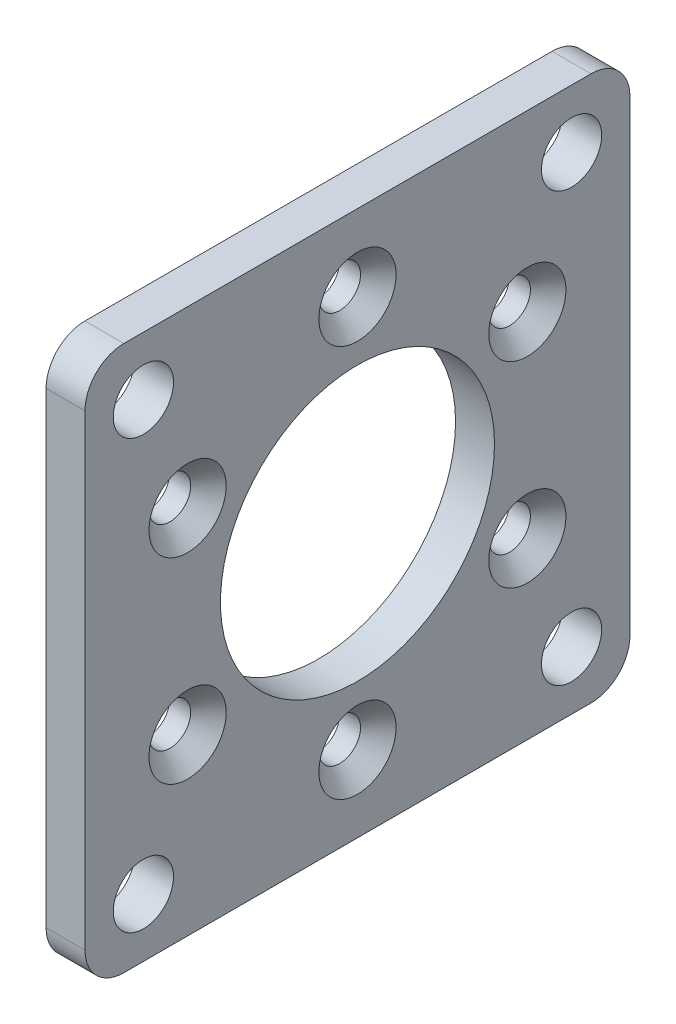
SolidWorks part; units mm, degrees
ref_plane "Front" through (0, 0, 0) normal (0, 0, 1) x (1, 0, 0)
ref_plane "Top" through (0, 0, 0) normal (0, 1, 0) x (1, 0, 0)
ref_plane "Right" through (0, 0, 0) normal (1, 0, 0) x (0, 0, -1)
sketch "Sketch1" plane through (0, 0, 0) normal (1, 0, 0) x (0, 0, -1)
  line L1 (22.225, -22.225) -> (-22.225, -22.225)
  line L2 (22.225, -22.225) -> (22.225, 22.225)
  line L3 (22.225, 22.225) -> (-22.225, 22.225)
  line L4 (-22.225, -22.225) -> (-22.225, 22.225)
  line L5 (22.225, -22.225) -> (-22.225, 22.225) construction
  line L6 (22.225, 22.225) -> (-22.225, -22.225) construction
  circle A0 centre (0, 0) radius 11.176
  dimension "D1" = 22.352
  dimension "D2" = 44.45
  dimension "D3" = 44.45
extrude "Boss-Extrude1" add sketch "Sketch1" along normal blind 3.175
sketch "Sketch4" plane through (3.175, 0, 0) normal (1, 0, 0) x (0, 0, -1)
  line L1 (22.225, 22.225) -> (-22.225, 22.225) construction
  line L2 (-22.225, 22.225) -> (-22.225, -22.225) construction
  line L3 (22.225, -22.225) -> (22.225, 22.225) construction
  line L4 (-22.225, -22.225) -> (22.225, -22.225) construction
  point P0 (-17.4625, 17.4625)
  point P2 (17.4625, 17.4625)
  point P4 (17.4625, -17.4625)
  point P6 (-17.4625, -17.4625)
  point P17 (-16.1195, 17.7425)
  point P18 (14.7376, 17.7425)
  point P19 (-17.7768, -17.2471)
  dimension "D1" = 4.7625
  dimension "D2" = 4.7625
  dimension "D3" = 4.7625
  dimension "D4" = 4.7625
hole_wizard "#10 (0.1935) Diameter Hole1" positions "Sketch4" profile "Sketch3" hole size "#10" standard "ANSI Inch" end condition up to next
sketch "Sketch3" plane through (3.175, 17.4625, 17.4625) normal (0, 1, 0) x (0, 0, -1)
  line L0 (0, 0) -> (0, 3.175)
  line L1 (0, 3.175) -> (2.4574, 3.175)
  line L2 (2.4574, 3.175) -> (2.4574, 0)
  line L5 (2.4574, 0) -> (0, 0)
  line L11 (0, -6.35) -> (0, 107.95) construction
  dimension "Thru Hole Dia." = 4.9149
  dimension "Thru Hole Depth" = 3.175
sketch "Sketch7" plane through (3.175, 0, 0) normal (1, 0, 0) x (0, 0, -1)
  circle A0 centre (0, 0) radius 16 construction
  point P5 (0, 16)
  point P11 (13.8564, 8)
  point P12 (13.8564, -8)
  point P13 (0, -16)
  point P14 (-13.8564, -8)
  point P15 (-13.8564, 8)
  dimension "D2" = 32
  dimension "D1" = 6
hole_wizard "CSK for M3 Flat Head Machine Screw1" positions "Sketch7" profile "Sketch6" countersink size "M3" standard "ANSI Metric" end condition up to next
sketch "Sketch6" plane through (3.175, 8, 13.8564) normal (0, 1, 0) x (0, 0, -1)
  line L0 (0, 0) -> (0, 3.175)
  line L1 (0, 3.175) -> (1.7, 3.175)
  line L2 (1.7, 3.175) -> (1.7, 1.45)
  line L3 (1.7, 1.45) -> (3.15, 0)
  line L5 (3.15, 0) -> (0, 0)
  line L6 (-1.7, 1.45) -> (-3.15, 0) construction
  line L11 (0, -6.35) -> (0, 107.95) construction
  dimension "Thru Hole Dia." = 3.4
  dimension "Thru Hole Depth" = 3.175
  dimension "Near C'Sink Dia." = 6.3
  dimension "Near C'Sink Angle" = 90
fillet "Fillet1" radius 3.175 4 edges at (1.5875, 22.225, 22.225) (1.5875, 22.225, -22.225) (1.5875, -22.225, -22.225) (1.5875, -22.225, 22.225)
